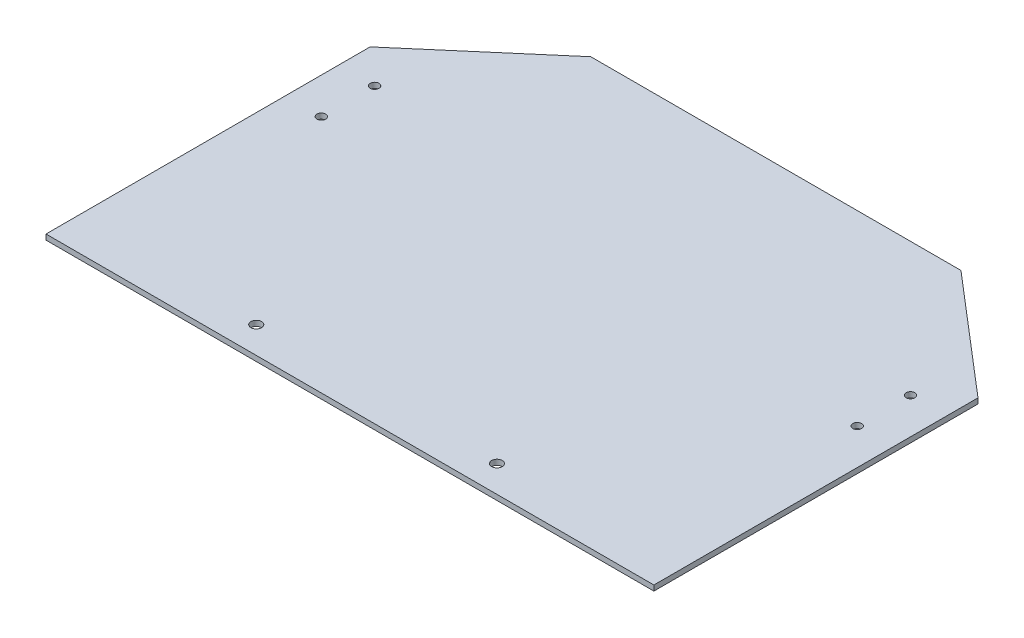
SolidWorks part; units mm, degrees
material "Nylon "
ref_plane "Plano frontal" through (0, 0, 0) normal (0, 0, 1) x (1, 0, 0)
ref_plane "Plano superior" through (0, 0, 0) normal (0, 1, 0) x (1, 0, 0)
ref_plane "Plano direito" through (0, 0, 0) normal (1, 0, 0) x (0, 0, -1)
sketch "Esboço1" plane through (0, 0, 0) normal (0, 1, 0) x (1, 0, 0)
  line L0 (-114, -79.875) -> (114, -79.875)
  line L1 (0, 79.875) -> (0, -79.875)
  line L2 (114, -79.875) -> (114, 41.685)
  line L3 (-69.415, 79.875) -> (69.415, 79.875)
  line L4 (69.415, 79.875) -> (114, 41.685)
  line L5 (-114, -79.875) -> (-114, 41.685)
  line L7 (-69.415, 79.875) -> (-114, 41.685)
  line L8 (51.996, -79.875) -> (51.996, -113.875)
  line L9 (51.996, -113.875) -> (114, -79.875)
  line L10 (-51, -79.875) -> (-51, -113.875)
  line L11 (-51, -113.875) -> (-114, -79.875)
  point P6 (114, -19.095)
  point P7 (0, 0)
  dimension "D1" = 228
  dimension "D2" = 159.75
  dimension "D3" = 121.56
  dimension "D4" = 138.83
  dimension "D5" = 63
  dimension "D6" = 62.004
  dimension "D7" = 34
  dimension "D8" = 34
extrude "Ressalto-extrusão1" add sketch "Esboço1" along normal blind 2 contours L3 L7 L5 L0 L1 | L4 L3 L1 L0 L2 region at (-54.9335, 0, 3.2928) region at (54.9335, 0, 3.2928)
ref_plane "Plano1" through (0, 0, -79.875) normal (0, 0, -1) x (-1, 0, 0)
sketch "Esboço3" plane through (0, 2, 0) normal (0, 1, 0) x (1, 0, 0)
  line L0 (-114, -79.875) -> (-114, 41.685) construction
  line L1 (-114, -79.875) -> (114, -79.875) construction
  line L2 (114, -79.875) -> (114, 41.685) construction
  line L5 (0, -1000) -> (0, 49000) construction
  circle A0 centre (-45.14, -69.875) radius 2
  circle A1 centre (45.14, -69.875) radius 2
  point P0 (-45.14, -69.875)
  point P5 (45.14, -69.875)
  dimension "D3" = 4
  dimension "D5" = 4
  dimension "D1" = 68.86
  dimension "D2" = 10
  dimension "D4" = 68.86
  dimension "D6" = 10
extrude "Corte-extrusão2" cut sketch "Esboço3" against normal blind 10
sketch "Esboço4" plane through (0, 2, 0) normal (0, 1, 0) x (1, 0, 0)
  line L8 (-114, -79.875) -> (114, -79.875) construction
  line L10 (-114, 41.685) -> (-114, -79.875)
  line L11 (-114, -79.875) -> (-102.536, -79.875)
  line L12 (-102.536, 75.0881) -> (-102.536, -79.875)
  line L13 (-102.536, 75.0881) -> (-102.536, 86.6244)
  line L15 (114, 41.685) -> (114, -79.875)
  line L16 (114, -79.875) -> (100.6429, -79.875)
  line L17 (100.6429, 75.0881) -> (100.6429, -79.875)
  line L18 (-102.536, 86.6244) -> (-114, 41.685)
  line L19 (100.6429, 75.0881) -> (100.6429, 88.8016)
  line L20 (100.6429, 88.8016) -> (114, 41.685)
extrude "Corte-extrusão4" [suppressed] cut sketch "Esboço4" against normal blind 10
move or copy body "Corpo-Converter em corpo de malha1" [suppressed] bodies to move or copy 110 copy no translate (0, 0, 0) parameters "D1"=0, "D2"=0, "D3"=0
sketch "Esboço5" plane through (0, 2, 0) normal (0, 1, 0) x (1, 0, 0)
  circle A0 centre (100.5, 29.877) radius 1.65
  circle A1 centre (100.5, 9.877) radius 1.65
  circle A2 centre (100.5, 9.877) radius 1.65 construction
  circle A3 centre (100.5, 29.877) radius 1.65 construction
  circle A4 centre (-100.5, 29.877) radius 1.65
  circle A5 centre (-100.5, 9.877) radius 1.65
  circle A6 centre (-100.5, 29.877) radius 1.65 construction
  circle A7 centre (-100.5, 9.877) radius 1.65 construction
extrude "Corte-extrusão5" cut sketch "Esboço5" against normal blind 2
